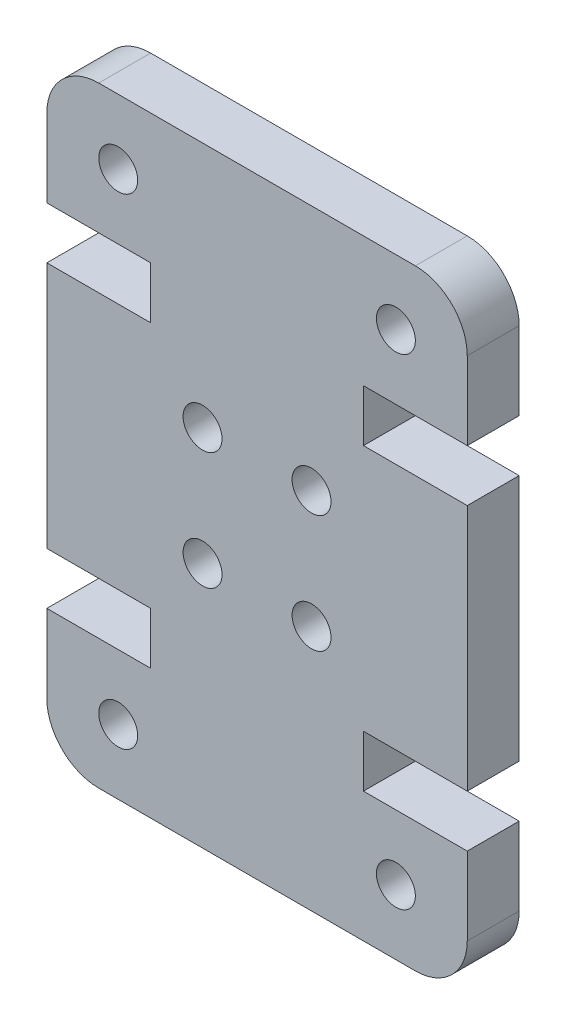
SolidWorks part; units mm, degrees
ref_plane "Front Plane" through (0, 0, 0) normal (0, 0, 1) x (1, 0, 0)
ref_plane "Top Plane" through (0, 0, 0) normal (0, 1, 0) x (1, 0, 0)
ref_plane "Right Plane" through (0, 0, 0) normal (1, 0, 0) x (0, 0, -1)
sketch "Sketch1" plane through (0, 0, 0) normal (0, 0, 1) x (1, 0, 0)
  line L20 (0, 7) -> (0, 16.53)
  line L21 (16.2, 16.53) -> (16.2, 7)
  line L22 (2, 23.53) -> (14.2, 23.53)
  line L23 (2, 0) -> (14.2, 0)
  line L24 (4, 18.53) -> (4, 16.53)
  line L25 (16.2, 18.53) -> (12.2, 18.53)
  line L26 (0, 18.53) -> (4, 18.53)
  line L27 (4, 16.53) -> (0, 16.53)
  line L28 (12.2, 18.53) -> (12.2, 16.53)
  line L29 (12.2, 16.53) -> (16.2, 16.53)
  line L30 (4, 7) -> (4, 5)
  line L31 (12.2, 7) -> (12.2, 5)
  line L32 (0, 7) -> (4, 7)
  line L33 (4, 5) -> (0, 5)
  line L34 (12.2, 5) -> (16.2, 5)
  line L35 (16.2, 7) -> (12.2, 7)
  line L36 (16.2, 21.53) -> (16.2, 18.53)
  line L37 (16.2, 5) -> (16.2, 2)
  line L38 (0, 21.53) -> (0, 18.53)
  line L39 (0, 5) -> (0, 2)
  circle A0 centre (10.2, 9.5) radius 0.75
  circle A1 centre (6, 9.5) radius 0.75
  circle A2 centre (6, 14.03) radius 0.75
  circle A3 centre (10.2, 14.03) radius 0.75
  arc A8 (2, 23.53) -> (0, 21.53) centre (2, 21.53) ccw
  arc A9 (16.2, 21.53) -> (14.2, 23.53) centre (14.2, 21.53) ccw
  arc A10 (14.2, 0) -> (16.2, 2) centre (14.2, 2) ccw
  arc A11 (0, 2) -> (2, 0) centre (2, 2) ccw
  circle A12 centre (13.45, 2.5) radius 0.75
  circle A13 centre (2.75, 2.5) radius 0.75
  circle A14 centre (13.45, 21.03) radius 0.75
  circle A15 centre (2.75, 21.03) radius 0.75
extrude "Boss-Extrude1" add sketch "Sketch1" along normal blind 2
